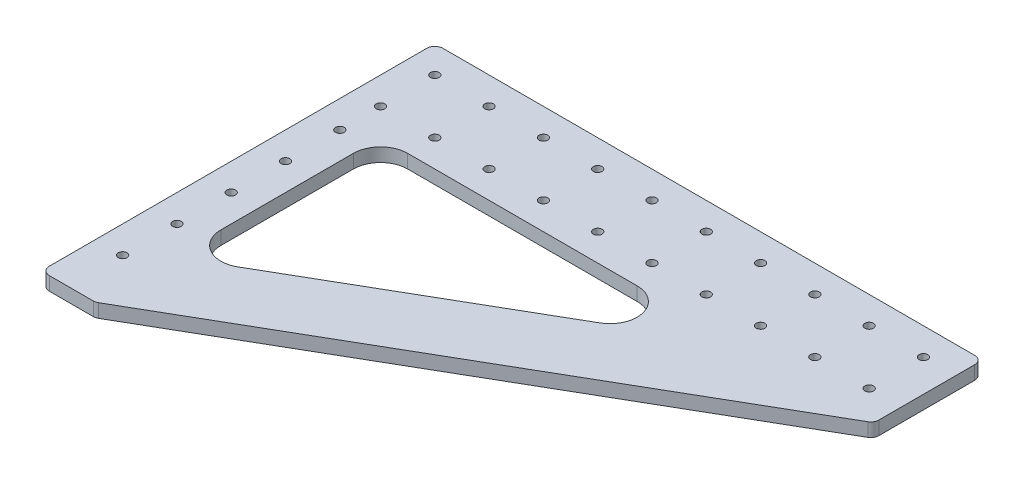
SolidWorks part; units mm, degrees
material "Hexcel AS4C (3000 丝)"
ref_plane "前视基准面" through (0, 0, 0) normal (0, 0, 1) x (1, 0, 0)
ref_plane "上视基准面" through (0, 0, 0) normal (0, 1, 0) x (1, 0, 0)
ref_plane "右视基准面" through (0, 0, 0) normal (1, 0, 0) x (0, 0, -1)
other "Configuration Table"
sketch "草图1" plane through (0, 0, 0) normal (0, 1, 0) x (1, 0, 0)
  line L0 (0, 0) -> (0, -105) construction
  line L1 (0, -105) -> (-20, -105)
  line L2 (-20, -105) -> (-20, 40)
  line L3 (-20, 40) -> (181.8653, 40)
  line L4 (181.8653, 40) -> (181.8653, 0)
  line L5 (181.8653, 0) -> (0, 0) construction
  line L6 (0, -105) -> (181.8653, 0)
  line L7 (0, -76.1325) -> (0, 0)
  line L8 (0, 0) -> (131.8653, 0)
  line L9 (131.8653, 0) -> (0, -76.1325)
  circle A0 centre (-10, -5) radius 1.6
  circle A1 centre (-10, -25) radius 1.6
  circle A2 centre (-10, -45) radius 1.6
  circle A3 centre (-10, 10) radius 1.6
  circle A4 centre (-10, 30) radius 1.6
  circle A5 centre (10, 30) radius 1.6
  circle A6 centre (10, 10) radius 1.6
  circle A7 centre (30, 30) radius 1.6
  circle A8 centre (30, 10) radius 1.6
  circle A9 centre (-10, -65) radius 1.6
  circle A10 centre (-10, -85) radius 1.6
  circle A11 centre (50, 10) radius 1.6
  circle A12 centre (70, 10) radius 1.6
  circle A13 centre (90, 10) radius 1.6
  circle A14 centre (110, 10) radius 1.6
  circle A15 centre (130, 10) radius 1.6
  circle A16 centre (150, 10) radius 1.6
  circle A17 centre (170, 10) radius 1.6
  circle A18 centre (50, 30) radius 1.6
  circle A19 centre (70, 30) radius 1.6
  circle A20 centre (90, 30) radius 1.6
  circle A21 centre (110, 30) radius 1.6
  circle A22 centre (130, 30) radius 1.6
  circle A23 centre (150, 30) radius 1.6
  circle A24 centre (170, 30) radius 1.6
  circle A25 centre (30, 30) radius 1.6
  dimension "D8" = 3.2
  dimension "D17" = 3.2
  dimension "D20" = 3.2
  dimension "D1" = 40
  dimension "D2" = 20
  dimension "D3" = 30
  dimension "D4" = 105
  dimension "D5" = 25
  dimension "D6" = 10
  dimension "D7" = 5
  dimension "D10" = 20
  dimension "D11" = 10
  dimension "D12" = 10
  dimension "D13" = 10
  dimension "D15" = 20
  dimension "D16" = 20
  dimension "D18" = 10
  dimension "D19" = 10
  dimension "D21" = 20
  dimension "D9" = 3
  dimension "D14" = 3
  dimension "D22" = 8
  dimension "D23" = 2
extrude "凸台-拉伸1" add sketch "草图1" along normal blind 5 contours L1 L6 L4 L3 L2 A24 A23 A22 A21 A20 A19 A18 A17 A16 A15 A14 A13 A12 A11 A10 A9 A8 A7 A6 A5 A4 A3 A2 region at (-10, 0, 102.5146)
fillet "圆角1" radius 10 3 edges at (0, 2.5, 0) (131.8653, 2.5, 0) (0, 2.5, 76.1325)
fillet "圆角2" radius 3 5 edges at (-20, 2.5, -40) (181.8653, 2.5, -40) (181.8653, 2.5, 0) (0, 2.5, 105) (-20, 2.5, 105)
ref_plane "基准面1" through (-20, 0, 0) normal (1, 0, 0) x (0, 0, -1)
